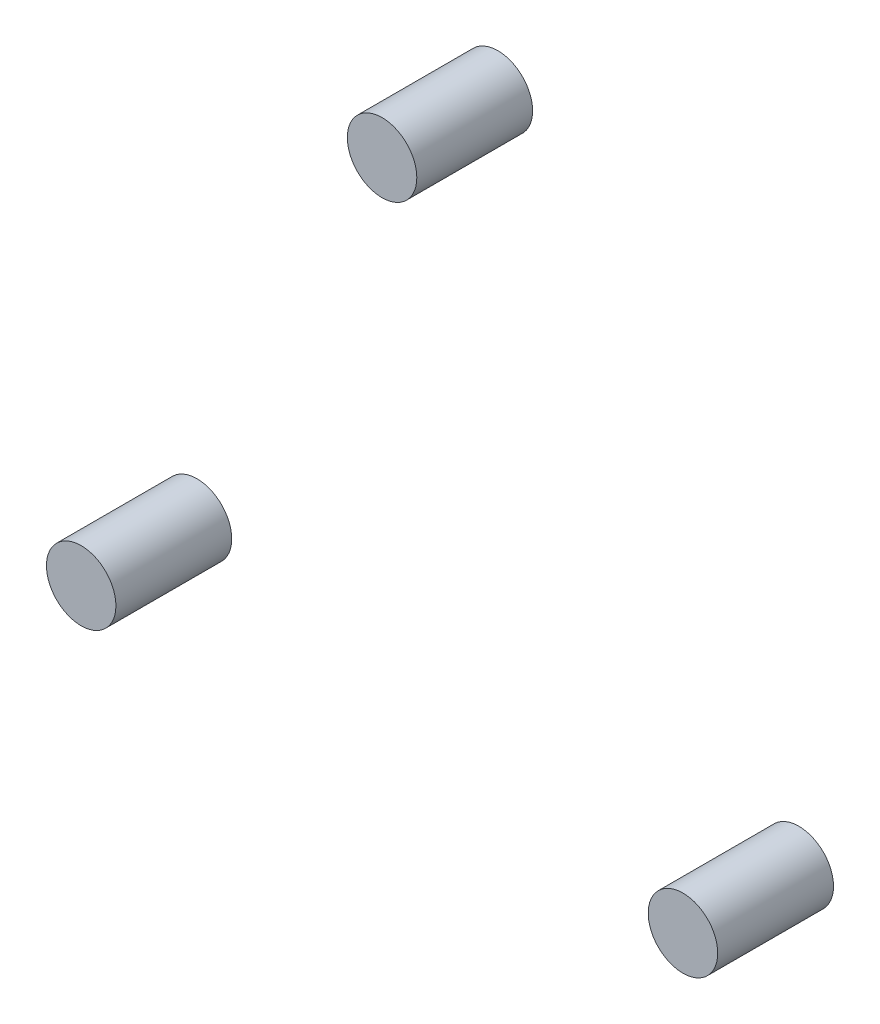
SolidWorks part; units mm, degrees
ref_plane "Ebene vorne" through (0, 0, 0) normal (0, 0, 1) x (1, 0, 0)
ref_plane "Ebene oben" through (0, 0, 0) normal (0, 1, 0) x (1, 0, 0)
ref_plane "Ebene rechts" through (0, 0, 0) normal (1, 0, 0) x (0, 0, -1)
sketch "Skizze1" plane through (0, 0, 0) normal (0, 0, 1) x (1, 0, 0)
  line L0 (0, 15) -> (0, 0) construction
  line L1 (0, 0) -> (12.9904, -7.5) construction
  line L2 (0, 0) -> (-12.9904, -7.5) construction
  line L3 (-12.9904, -7.5) -> (12.9904, -7.5) construction
  circle A0 centre (0, 15) radius 1.5
  circle A1 centre (12.9904, -7.5) radius 1.5
  circle A2 centre (-12.9904, -7.5) radius 1.5
  circle A3 centre (0, 0) radius 15 construction
  dimension "W" = 3
  dimension "D" = 30
  dimension "alpha" = 120
  dimension "D4" = 120
  dimension "D5" = 120
extrude "Aufsatz-Linear austragen1" add sketch "Skizze1" against normal blind 5
ref_axis "Achse1" through (0, 0, 0.25) along (0, 0, -1)
